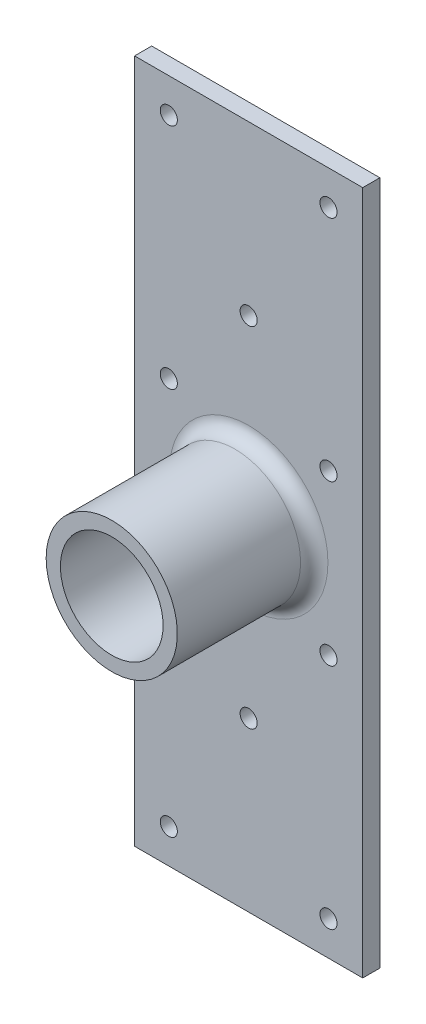
SolidWorks part; units mm, degrees
ref_plane "Front Plane" through (0, 0, 0) normal (0, 0, 1) x (1, 0, 0)
ref_plane "Top Plane" through (0, 0, 0) normal (0, 1, 0) x (1, 0, 0)
ref_plane "Right Plane" through (0, 0, 0) normal (1, 0, 0) x (0, 0, -1)
sketch "Sketch1" plane through (0, 0, 0) normal (0, 0, 1) x (1, 0, 0)
  line L5 (-31.75, 95.25) -> (31.75, 95.25)
  line L6 (-31.75, 95.25) -> (-31.75, -95.25)
  line L7 (-31.75, -95.25) -> (31.75, -95.25)
  line L8 (31.75, 95.25) -> (31.75, -95.25)
  line L9 (-31.75, 95.25) -> (31.75, -95.25) construction
  line L10 (-31.75, -95.25) -> (31.75, 95.25) construction
  point P5 (0, 0)
  dimension "D1" = 63.5
  dimension "D2" = 190.5
extrude "Boss-Extrude1" add sketch "Sketch1" along normal blind 4.7625
sketch "Sketch3" plane through (0, 0, 4.7625) normal (0, 0, 1) x (1, 0, 0)
  circle A0 centre (0, 0) radius 6.35
  dimension "D1" = 12.7
extrude "Cut-Extrude1" cut sketch "Sketch3" against normal blind 0.508
sketch "Sketch4" plane through (0, 0, 4.7625) normal (0, 0, 1) x (1, 0, 0)
  circle A0 centre (0, 0) radius 18.2562
  dimension "D1" = 36.5125
extrude "Boss-Extrude2" add sketch "Sketch4" along normal blind 38.1 contours A0
sketch "Sketch5" plane through (0, 0, 42.8625) normal (0, 0, 1) x (1, 0, 0)
  circle A0 centre (0, 0) radius 12.4619
  dimension "D1" = 24.9237
extrude "Cut-Extrude2" cut sketch "Sketch5" against normal blind 38.1 contours A0
sketch "Sketch7" plane through (0, 0, 42.8625) normal (0, 0, 1) x (1, 0, 0)
  circle A0 centre (0, 0) radius 14.2875
  dimension "D1" = 28.575
extrude "Cut-Extrude3" cut sketch "Sketch7" against normal blind 30.48
fillet "Fillet1" radius 3.81 1 edges at (18.2562, 0, 4.7625)
hole_wizard "3/16 (0.1875) Diameter Hole1" positions "Sketch8" profile "Sketch9" hole size "3/16" standard "ANSI Inch" end condition through all
sketch "Sketch8" plane through (0, 0, 4.7625) normal (0, 0, 1) x (1, 0, 0)
  line L0 (31.75, 95.25) -> (-31.75, 95.25) construction
  line L1 (31.75, -95.25) -> (31.75, 95.25) construction
  line L2 (-31.75, 95.25) -> (-31.75, -95.25) construction
  line L3 (-31.75, -95.25) -> (31.75, -95.25) construction
  point P0 (-22.225, 85.725)
  point P2 (-22.225, -85.725)
  point P4 (22.225, -85.725)
  point P6 (22.225, 85.725)
  point P17 (0, 48.514)
  point P19 (0, -48.514)
  point P23 (-22.225, 22.225)
  point P26 (-22.225, -22.225)
  point P28 (22.225, -22.225)
  point P30 (22.225, 22.225)
  dimension "D1" = 9.525
  dimension "D2" = 9.525
  dimension "D3" = 9.525
  dimension "D4" = 9.525
  dimension "D5" = 9.525
  dimension "D6" = 9.525
  dimension "D7" = 9.525
  dimension "D8" = 9.525
  dimension "D9" = 48.514
  dimension "D10" = 48.514
  dimension "D11" = 63.5
  dimension "D12" = 63.5
  dimension "D13" = 63.5
  dimension "D14" = 63.5
sketch "Sketch9" plane through (-22.225, 85.725, 4.7625) normal (1, 0, 0) x (0, -1, 0)
  line L0 (0, 0) -> (0, 4.7625)
  line L1 (0, 4.7625) -> (2.3812, 4.7625)
  line L2 (2.3812, 4.7625) -> (2.3812, 0)
  line L5 (2.3812, 0) -> (0, 0)
  line L11 (0, -6.35) -> (0, 107.95) construction
  dimension "Thru Hole Dia." = 4.7625
  dimension "Thru Hole Depth" = 4.7625
sketch "Sketch10" plane through (0, 0, 4.7625) normal (0, 0, 1) x (1, 0, 0)
  line L0 (31.75, 31.75) -> (-31.75, 31.75)
  line L1 (31.75, -95.25) -> (31.75, 95.25) construction
  line L2 (-31.75, 95.25) -> (-31.75, -95.25) construction
  line L3 (31.75, -31.75) -> (-31.75, -31.75)
  point P8 (-31.75, 0)
  dimension "D1" = 31.75
  dimension "D2" = 31.75
